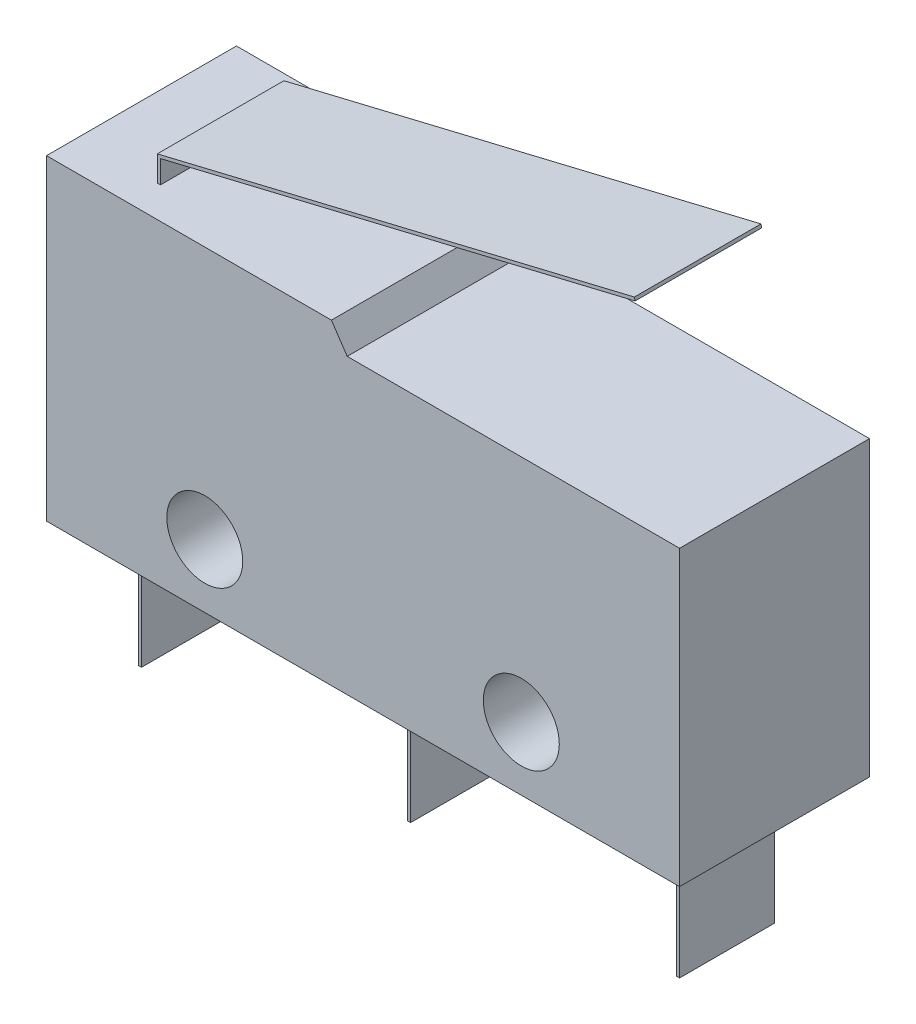
SolidWorks part; units mm, degrees
ref_plane "Front" through (0, 0, 0) normal (0, 0, 1) x (1, 0, 0)
ref_plane "Top" through (0, 0, 0) normal (0, 1, 0) x (1, 0, 0)
ref_plane "Right" through (0, 0, 0) normal (1, 0, 0) x (0, 0, -1)
sketch "Sketch1" plane through (0, 0, 0) normal (0, 0, 1) x (1, 0, 0)
  line L0 (-1, 5) -> (-0.5, 4.2583)
  line L1 (-10, 5) -> (10, 5)
  line L2 (-10, 5) -> (-10, -5)
  line L3 (-10, -5) -> (10, -5)
  line L4 (10, 5) -> (10, -5)
  line L5 (-10, 5) -> (10, -5) construction
  line L6 (-10, -5) -> (10, 5) construction
  line L7 (-0.5, 4.2583) -> (10, 4.2583)
  circle A0 centre (-5, -3) radius 1.2
  circle A1 centre (5, -3) radius 1.2
  point P0 (0, 0)
  dimension "D3" = 2.4
  dimension "D1" = 20
  dimension "D2" = 10
  dimension "D4" = 2
  dimension "D5" = 5
  dimension "D6" = 5
  dimension "D7" = 9
  dimension "D8" = 10.5
extrude "Boss-Extrude1" add sketch "Sketch1" along normal blind 6 contours L7 L0 L1 L2 L3 L4 A1 A0 region at (-0.2015, -0.0535, 0)
sketch "Sketch2" plane through (0, 0, 6) normal (0, 0, 1) x (1, 0, 0)
  line L0 (-7.5, 5) -> (-7.5, 5.8)
  line L2 (-7.5, 5.8) -> (7.5717, 9.4184)
  line L4 (-10, 5) -> (-1, 5) construction
  line L5 (-10, 5) -> (-10, -5) construction
  point P2 (0, 0)
  point P3 (0, 0)
  point P9 (0, 0)
  point P10 (0, 0)
  point P11 (0, 0)
  dimension "D1" = 0.8
  dimension "D2" = 13.5
  dimension "D3" = 15.5
  dimension "D4" = 2.5
extrude "Extrude-Thin1" add sketch "Sketch2" against normal blind 4 from offset 1 thin contours L0 L2 offset against normal yes thin type one direction wall 0.1
sketch "Sketch3" plane through (0, -5, 0) normal (0, -1, 0) x (1, 0, 0)
  line L0 (-8.5, 4.5) -> (-8.5, 1.5)
  line L1 (-10, 6) -> (-10, 0) construction
  line L2 (-10, 6) -> (10, 6) construction
  line L3 (0, -55) -> (0, 55) construction
  line L4 (8.5, 4.5) -> (8.5, 1.5)
  line L5 (0, 4.5) -> (0, 1.5)
  dimension "D1" = 3
  dimension "D2" = 1.5
  dimension "D3" = 1.5
extrude "Extrude-Thin2" add sketch "Sketch3" along normal blind 4 thin thin type one direction wall 0.1
